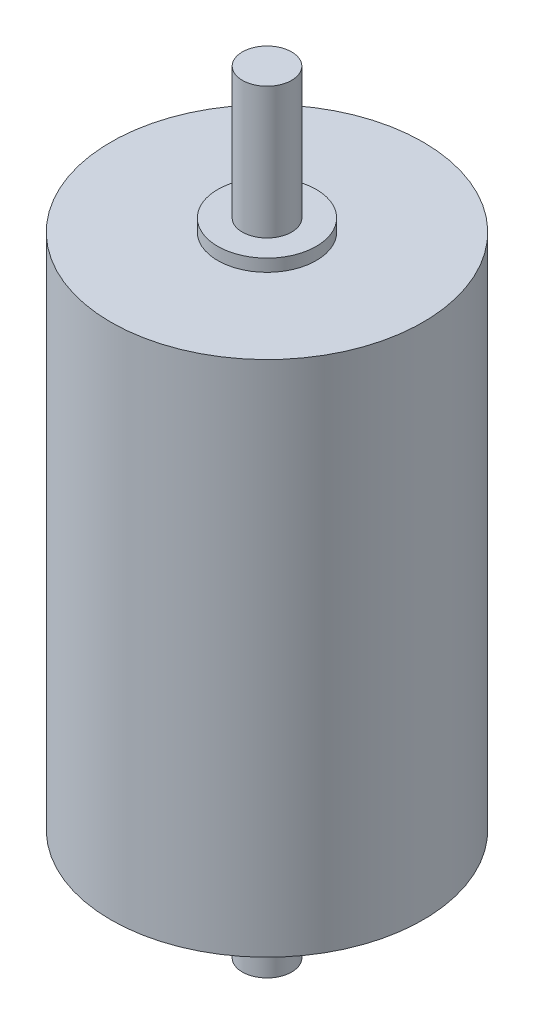
SolidWorks part; units mm, degrees
ref_plane "Face" through (0, 0, 0) normal (0, 0, 1) x (1, 0, 0)
ref_plane "Dessus" through (0, 0, 0) normal (0, 1, 0) x (1, 0, 0)
ref_plane "Droite" through (0, 0, 0) normal (1, 0, 0) x (0, 0, -1)
sketch "Esquisse1" plane through (0, 0, 0) normal (0, 0, 1) x (1, 0, 0)
  line L0 (0, 0) -> (0, 94)
  line L1 (0, 94) -> (3, 94)
  line L2 (3, 94) -> (3, 78)
  line L3 (3, 78) -> (6, 78)
  line L4 (6, 78) -> (6, 76.5)
  line L5 (6, 76.5) -> (19, 76.5)
  line L6 (19, 76.5) -> (19, 13.5)
  line L7 (19, 13.5) -> (6, 13.5)
  line L8 (6, 13.5) -> (6, 12)
  line L9 (6, 12) -> (3, 12)
  line L10 (3, 12) -> (3, 0)
  line L11 (3, 0) -> (0, 0)
  dimension "D1" = 19
  dimension "D2" = 63
  dimension "D3" = 3
  dimension "D4" = 6
  dimension "D5" = 1.5
  dimension "D6" = 12
  dimension "D7" = 16
revolve "Révolution1" add sketch "Esquisse1" angle 360 about L0
